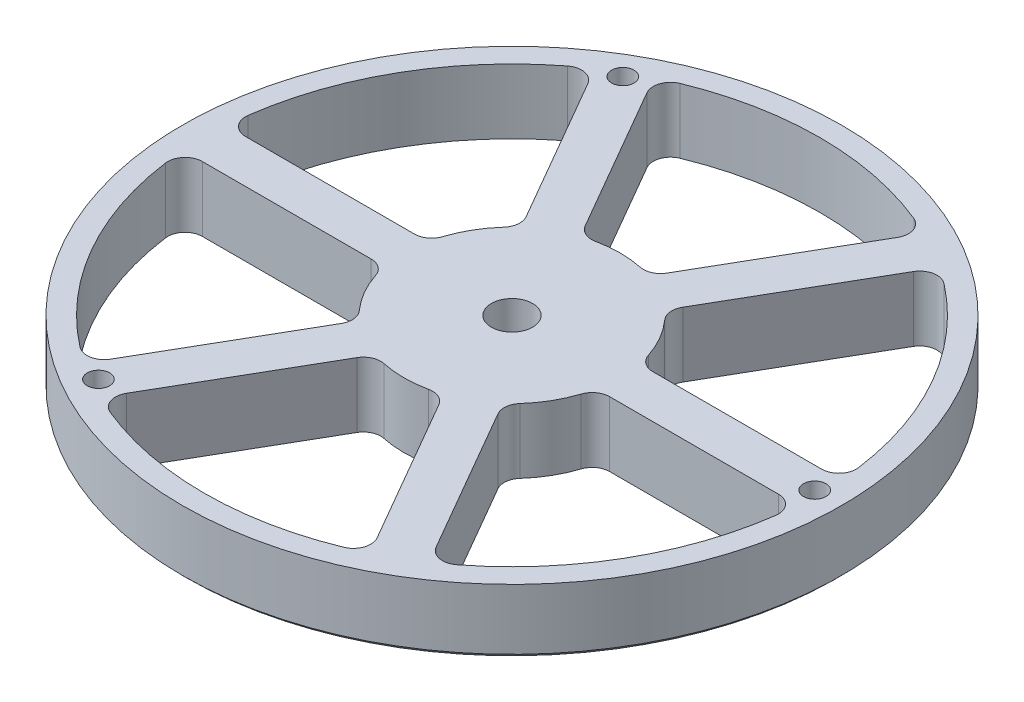
SolidWorks part; units mm, degrees
ref_plane "Front Plane" through (0, 0, 0) normal (0, 0, 1) x (1, 0, 0)
ref_plane "Top Plane" through (0, 0, 0) normal (0, 1, 0) x (1, 0, 0)
ref_plane "Right Plane" through (0, 0, 0) normal (1, 0, 0) x (0, 0, -1)
sketch "Sketch2" plane through (0, 0, 0) normal (1, 0, 0) x (0, 0, -1)
  line L0 (0, 0) -> (-76.2, 0)
  line L1 (-76.2, 0) -> (-76.2, 15)
  line L2 (-76.2, 15) -> (0, 15)
  line L5 (0, 15) -> (0, 0)
  dimension "D1" = 76.2
  dimension "D2" = 15
ref_axis "Axis1" through (0, -0.75, 0) along (0, 1, 0)
revolve "Revolve1" add sketch "Sketch2" angle 360 about axis through (0, -0.75, 0) along (0, 1, 0)
hole_wizard "#6 (0.204) Diameter Hole1" positions "Sketch6" profile "Sketch7" hole size "#6" standard "ANSI Inch" end condition through all
sketch "Sketch6" plane through (0, 15, 0) normal (0, 1, 0) x (1, 0, 0)
  line L0 (0, 0) -> (-69.8201, 120.932) construction
  line L2 (0, 0) -> (0, 109.0908) construction
  point P0 (-35, 60.6218)
  dimension "D1" = 30
  dimension "D2" = 70
sketch "Sketch7" plane through (-35, 15, -60.6218) normal (1, 0, 0) x (0, 0, 1)
  line L0 (0, 0) -> (0, 15)
  line L1 (0, 15) -> (2.5908, 15)
  line L2 (2.5908, 15) -> (2.5908, 0)
  line L5 (2.5908, 0) -> (0, 0)
  line L11 (0, -6.35) -> (0, 107.95) construction
  dimension "Thru Hole Dia." = 5.1816
  dimension "Thru Hole Depth" = 15
pattern_circular "CirPattern3" count 3 over 360 about axis through (0, -0.75, 0) along (0, 1, 0) of "#6 (0.204) Diameter Hole1"
sketch "Sketch8" plane through (0, 15, 0) normal (0, 1, 0) x (1, 0, 0)
  line L4 (0, 0) -> (0, 93.9995) construction
  line L5 (0, 0) -> (113.8372, 0) construction
  line L6 (-7.9173, 23.7132) -> (-31.182, 64.0088)
  line L7 (7.9173, 23.7132) -> (31.182, 64.0088)
  line L8 (0, 0) -> (-35, 60.6218) construction
  arc A0 (-7.9173, 23.7132) -> (7.9173, 23.7132) centre (0, 0) cw
  arc A1 (-31.182, 64.0088) -> (31.182, 64.0088) centre (0, 0) cw
  circle A2 centre (0, 0) radius 76.2 construction
  dimension "D1" = 25
  dimension "D2" = 5
  dimension "D3" = 5
extrude "Cut-Extrude1" cut sketch "Sketch8" against normal through all
fillet "Fillet1" radius 4 4 edges at (7.9173, 7.5, -23.7132) (31.182, 7.5, -64.0088) (-7.9173, 7.5, -23.7132) (-31.182, 7.5, -64.0088)
pattern_circular "CirPattern4" count 6 over 360 about axis through (0, -0.75, 0) along (0, 1, 0) of "Cut-Extrude1", "Fillet1"
chamfer "Chamfer2" distance 1 angle 45 1 edges at (0, 0, -76.2)
hole_wizard "3/8 (0.375) Diameter Hole1" positions "Sketch9" profile "Sketch11" hole size "3/8" standard "ANSI Inch" end condition through all
sketch "Sketch9" plane through (0, 0, 0) normal (0, -1, 0) x (-1, 0, 0)
  point P0 (0, 0)
sketch "Sketch11" plane through (0, 0, 0) normal (1, 0, 0) x (0, 0, -1)
  line L0 (0, 0) -> (0, 15)
  line L1 (0, 15) -> (4.7625, 15)
  line L2 (4.7625, 15) -> (4.7625, 0)
  line L5 (4.7625, 0) -> (0, 0)
  line L11 (0, -6.35) -> (0, 107.95) construction
  dimension "Thru Hole Dia." = 9.525
  dimension "Thru Hole Depth" = 15
equation "\"TubeDiameter\" = 6.000in"
equation "\"D1@Sketch2\"=\"TubeDiameter\"/2"
